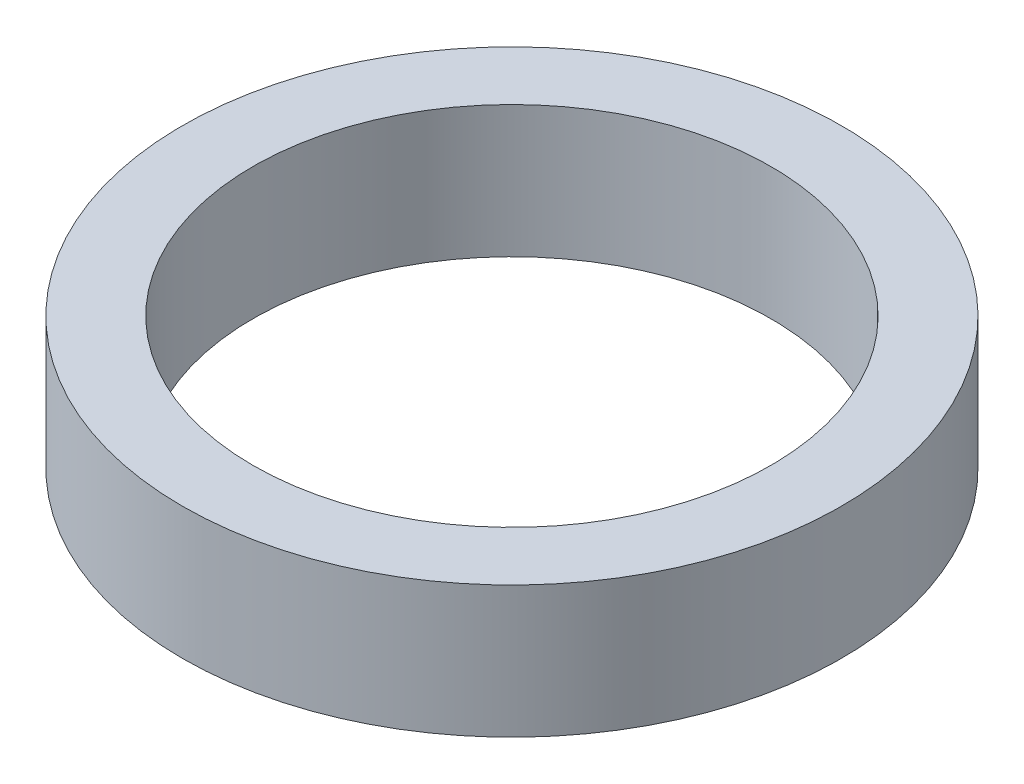
SolidWorks part; units mm, degrees
ref_plane "Front Plane" through (0, 0, 0) normal (0, 0, 1) x (1, 0, 0)
ref_plane "Top Plane" through (0, 0, 0) normal (0, 1, 0) x (1, 0, 0)
ref_plane "Right Plane" through (0, 0, 0) normal (1, 0, 0) x (0, 0, -1)
sketch "Sketch1" plane through (0, 0, 0) normal (0, 1, 0) x (1, 0, 0)
  circle A0 centre (0, 0) radius 35
  dimension "FLANGE_OD" = 70
extrude "Boss-Extrude1" add sketch "Sketch1" along normal blind 14
sketch "Sketch2" plane through (0, 0, 0) normal (0, 1, 0) x (1, 0, 0)
  circle A0 centre (0, 0) radius 27.5
  dimension "BORE_D" = 55
extrude "Cut-Extrude1" cut sketch "Sketch2" along normal through all
sketch "Sketch3" plane through (0, 14, 0) normal (0, 1, 0) x (1, 0, 0)
  circle A0 centre (0, 0) radius 15.6804 construction
  circle A1 centre (-15.6804, 0) radius 1.5
  dimension "BOLT_D" = 3
  dimension "BOLT_PCD" = 31.3608
extrude "Cut-Extrude2" cut sketch "Sketch3" against normal blind 11.8896 rebuild error yes
pattern_circular "CirPattern1" count 5 over 360 rebuild error yes
